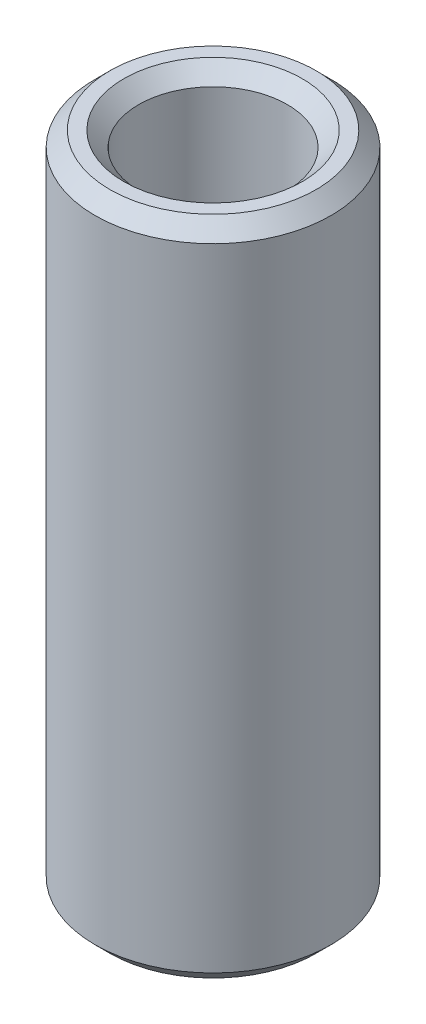
SolidWorks part; units mm, degrees
ref_plane "Front Plane" through (0, 0, 0) normal (0, 0, 1) x (1, 0, 0)
ref_plane "Top Plane" through (0, 0, 0) normal (0, 1, 0) x (1, 0, 0)
ref_plane "Right Plane" through (0, 0, 0) normal (1, 0, 0) x (0, 0, -1)
sketch "Sketch1" plane through (0, 0, 0) normal (0, 1, 0) x (1, 0, 0)
  circle A0 centre (0, 0) radius 30
  dimension "SLEEVE_OD" = 60
extrude "Boss-Extrude1" add sketch "Sketch1" along normal blind 168.1398
sketch "Sketch2" plane through (0, 0, 0) normal (0, 1, 0) x (1, 0, 0)
  circle A0 centre (0, 0) radius 18.8886
  dimension "BORE_D" = 37.7773
extrude "Cut-Extrude1" cut sketch "Sketch2" along normal through all
chamfer "Chamfer1" distance 3.7987 angle 45 4 edges at (0, 168.1398, 18.8886) (0, 0, 18.8886) (0, 0, 30) (0, 168.1398, 30)
